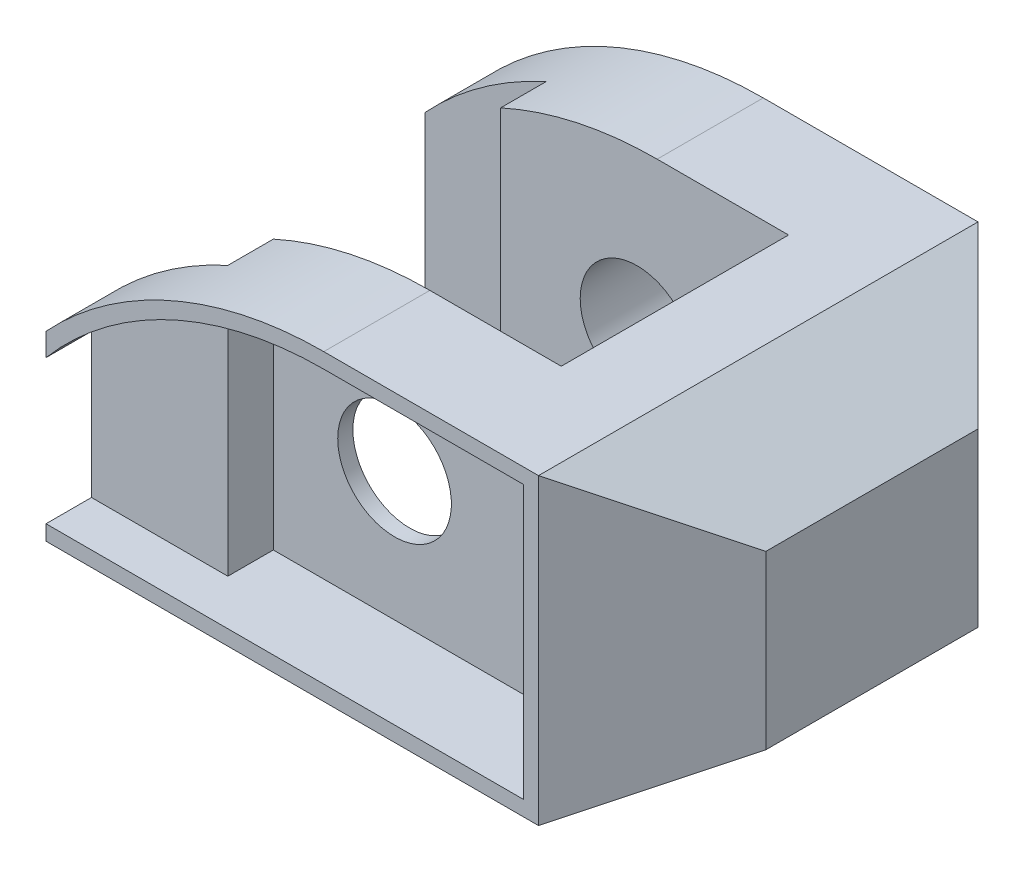
SolidWorks part; units mm, degrees
material "1060 Alloy"
ref_plane "Front Plane" through (0, 0, 0) normal (0, 0, 1) x (1, 0, 0)
ref_plane "Top Plane" through (0, 0, 0) normal (0, 1, 0) x (1, 0, 0)
ref_plane "Right Plane" through (0, 0, 0) normal (1, 0, 0) x (0, 0, -1)
sketch "Sketch1" plane through (0, 0, 0) normal (0, 0, 1) x (1, 0, 0)
  line L0 (0, 0) -> (65, 0)
  line L1 (65, 0) -> (80, 8.6603)
  line L2 (80, 8.6603) -> (80, 31.3397)
  line L3 (80, 31.3397) -> (65, 40)
  line L4 (0, 0) -> (0, 24)
  line L5 (65, 40) -> (36.6606, 40)
  line L6 (0, 19) -> (80, 19) construction
  line L7 (34, 0) -> (34, 19) construction
  arc A0 (36.6606, 40) -> (0, 24) centre (36.6606, -10) ccw
  circle A1 centre (34, 19) radius 7.5
  dimension "D8" = 50
  dimension "D11" = 15
  dimension "D1" = 65
  dimension "D2" = 24
  dimension "D3" = 30
  dimension "D4" = 30
  dimension "D5" = 40
  dimension "D6" = 15
  dimension "D7" = 15
  dimension "D9" = 19
  dimension "D10" = 31
extrude "Boss-Extrude1" add sketch "Sketch1" along normal blind 58
sketch "Sketch2" plane through (0, 0, 0) normal (0, 1, 0) x (1, 0, 0)
  line L0 (0, -58) -> (0, 0) construction
  line L1 (0, -8) -> (16, -8)
  line L2 (0, -8) -> (0, -50)
  line L3 (0, -50) -> (16, -50)
  line L4 (16, -8) -> (16, -50)
  line L5 (36.6606, 0) -> (0, 0) construction
  line L6 (0, -58) -> (36.6606, -58) construction
  dimension "D1" = 8
  dimension "D2" = 8
  dimension "D3" = 16
extrude "Cut-Extrude1" cut sketch "Sketch2" along normal through all
sketch "Sketch3" plane through (0, 0, 0) normal (0, 1, 0) x (1, 0, 0)
  line L0 (16, -50) -> (16, -8) construction
  line L1 (16, -14) -> (54, -14)
  line L2 (16, -14) -> (16, -44)
  line L3 (16, -44) -> (54, -44)
  line L4 (54, -14) -> (54, -44)
  line L5 (65, -58) -> (65, 0) construction
  line L6 (0, -8) -> (16, -8) construction
  line L7 (16, -50) -> (0, -50) construction
  dimension "D1" = 11
  dimension "D2" = 6
  dimension "D3" = 6
extrude "Cut-Extrude2" cut sketch "Sketch3" along normal through all
sketch "Sketch4" plane through (0, 0, 0) normal (0, 1, 0) x (1, 0, 0)
  line L0 (65, 0) -> (80, -15)
  line L1 (80, -58) -> (80, 0) construction
  line L2 (80, -15) -> (80, 0)
  line L3 (80, 0) -> (65, 0)
  line L4 (65, -58) -> (80, -43)
  line L5 (80, -43) -> (80, -58)
  line L6 (80, -58) -> (65, -58)
  line L7 (65, 0) -> (36.6606, 0) construction
  line L8 (65, -58) -> (36.6606, -58) construction
  dimension "D1" = 45
  dimension "D2" = 45
extrude "Cut-Extrude3" cut sketch "Sketch4" along normal through all
sketch "Sketch5" plane through (0, 0, 58) normal (0, 0, 1) x (1, 0, 0)
  line L0 (0, 24) -> (0, 0) construction
  line L6 (0, 2) -> (0, 20.9839)
  line L9 (0, 2) -> (63, 2)
  line L10 (63, 2) -> (63, 38)
  line L11 (63, 38) -> (36.6606, 38)
  line L12 (0, 2) -> (63, 2)
  line L13 (63, 2) -> (63, 38)
  line L14 (63, 38) -> (36.6606, 38)
  arc A5 (36.6606, 38) -> (1.4664, 22.64) centre (36.6606, -10) ccw
  arc A6 (36.6606, 38) -> (0, 20.9839) centre (36.6606, -10) ccw
  point P0 (0, 20.9865)
  dimension "D1" = 2
extrude "Cut-Extrude4" cut sketch "Sketch5" against normal blind 6
sketch "Sketch6" plane through (0, 0, 52) normal (0, 0, 1) x (1, 0, 0)
  line L12 (0, 20.9839) -> (0, 2)
  line L13 (0, 2) -> (63, 2)
  line L14 (63, 2) -> (63, 38)
  line L15 (63, 38) -> (36.6606, 38)
  line L16 (0, 20.9839) -> (0, 2)
  line L17 (0, 2) -> (63, 2)
  line L18 (63, 2) -> (63, 38)
  line L19 (63, 38) -> (36.6606, 38)
  arc A3 (36.6606, 38) -> (0, 20.9839) centre (36.6606, -10) ccw
  arc A4 (36.6606, 38) -> (0, 20.9839) centre (36.6606, -10) ccw
  dimension "D1" = 0
sketch "Sketch7" plane through (0, 0, 52) normal (0, 0, 1) x (1, 0, 0)
  line L1 (18, 34.2242) -> (18, 2)
  line L4 (0, 20.9839) -> (0, 2)
  line L5 (0, 2) -> (63, 2)
  line L6 (63, 2) -> (63, 38)
  line L7 (63, 38) -> (36.6606, 38)
  line L9 (18, 2) -> (63, 2)
  line L10 (63, 2) -> (63, 38)
  line L11 (63, 38) -> (36.6606, 38)
  arc A1 (36.6606, 38) -> (0, 20.9839) centre (36.6606, -10) ccw
  arc A2 (36.6606, 38) -> (18, 34.2242) centre (36.6606, -10) ccw
  dimension "D1" = 0
extrude "Cut-Extrude5" cut sketch "Sketch7" against normal blind 6
equation "\"a\"= 58mm"
equation "\"b\"= 40mm"
equation "\"c\"= 65mm"
